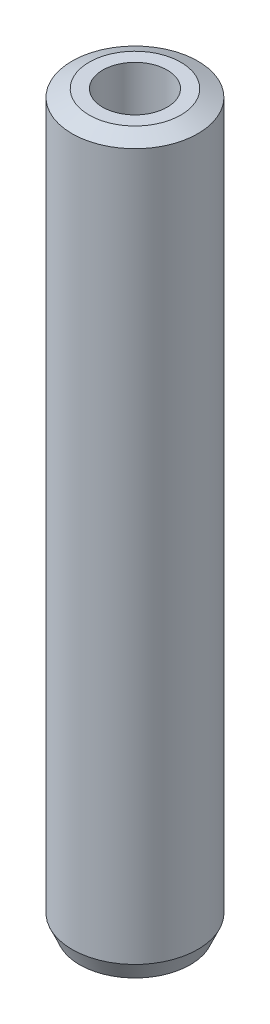
SolidWorks part; units mm, degrees
ref_plane "Front Plane" through (0, 0, 0) normal (0, 0, 1) x (1, 0, 0)
ref_plane "Top Plane" through (0, 0, 0) normal (0, 1, 0) x (1, 0, 0)
ref_plane "Right Plane" through (0, 0, 0) normal (1, 0, 0) x (0, 0, -1)
sketch "Sketch1" plane through (0, 0, 0) normal (0, 1, 0) x (1, 0, 0)
  circle A0 centre (0, 0) radius 17.5
  dimension "SHAFT_OD" = 35
extrude "Boss-Extrude1" add sketch "Sketch1" along normal blind 203.3449
sketch "Sketch2" plane through (0, 0, 0) normal (0, 1, 0) x (1, 0, 0)
  circle A0 centre (0, 0) radius 8.9653
  dimension "BORE_D" = 17.9307
extrude "Cut-Extrude1" cut sketch "Sketch2" along normal through all
chamfer "Chamfer1" distance 2.1051 angle 66.123 2 edges at (0, 203.3449, 17.5) (0, 0, 17.5) first distance on face at (0, 203.3449, 17.5) first distance on face at (0, 0, 8.9653)
